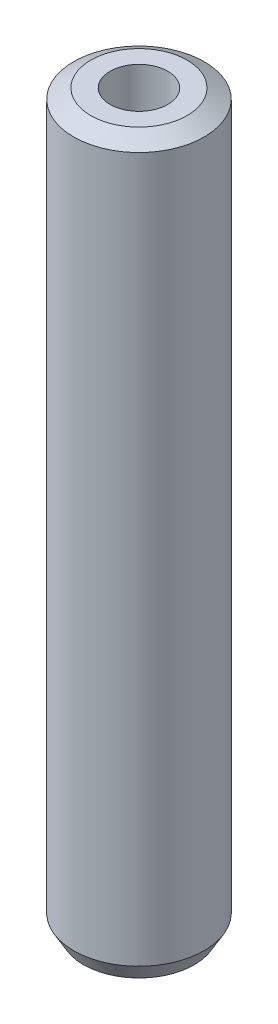
SolidWorks part; units mm, degrees
ref_plane "Front Plane" through (0, 0, 0) normal (0, 0, 1) x (1, 0, 0)
ref_plane "Top Plane" through (0, 0, 0) normal (0, 1, 0) x (1, 0, 0)
ref_plane "Right Plane" through (0, 0, 0) normal (1, 0, 0) x (0, 0, -1)
sketch "Sketch1" plane through (0, 0, 0) normal (0, 1, 0) x (1, 0, 0)
  circle A0 centre (0, 0) radius 20
  dimension "SHAFT_OD" = 40
extrude "Boss-Extrude1" add sketch "Sketch1" along normal blind 224.2067
sketch "Sketch2" plane through (0, 0, 0) normal (0, 1, 0) x (1, 0, 0)
  circle A0 centre (0, 0) radius 8.8321
  dimension "BORE_D" = 17.6642
extrude "Cut-Extrude1" cut sketch "Sketch2" along normal through all
chamfer "Chamfer1" distance 3.0352 angle 60 2 edges at (0, 224.2067, 20) (0, 0, 20) first distance on face at (0, 224.2067, 20) first distance on face at (0, 0, 8.8321)
